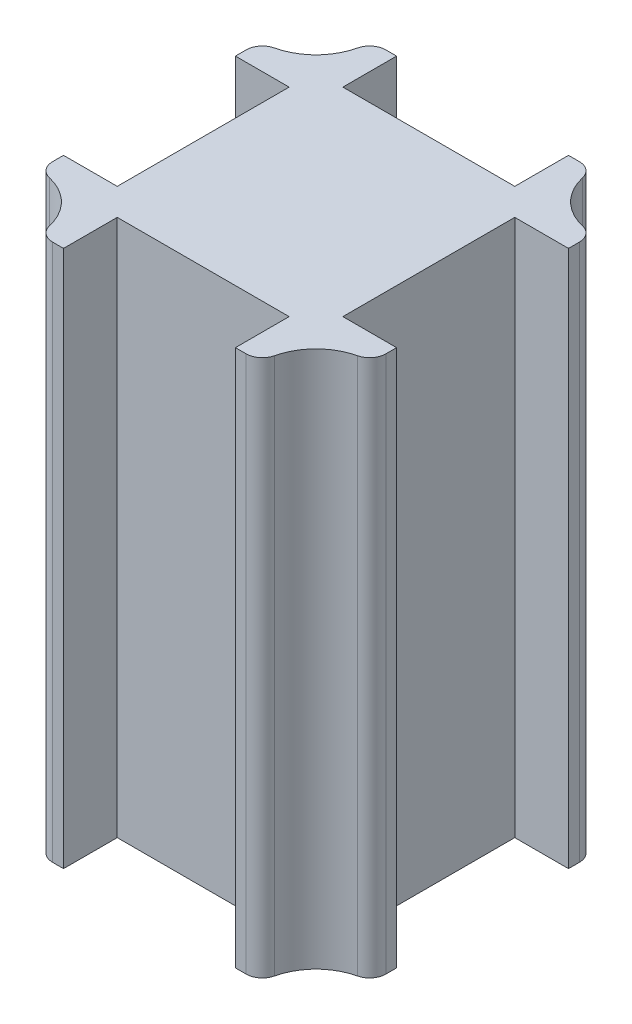
SolidWorks part; units mm, degrees
ref_plane "Front Plane" through (0, 0, 0) normal (0, 0, 1) x (1, 0, 0)
ref_plane "Top Plane" through (0, 0, 0) normal (0, 1, 0) x (1, 0, 0)
ref_plane "Right Plane" through (0, 0, 0) normal (1, 0, 0) x (0, 0, -1)
sketch "Sketch5" plane through (0, 3, 0) normal (0, 1, 0) x (1, 0, 0)
  line L0 (7.5, -348) -> (7.5, 348) construction
  line L1 (-15.5, 15.5) -> (15.5, 15.5)
  line L2 (-15.5, 15.5) -> (-15.5, -15.5)
  line L3 (-15.5, -15.5) -> (15.5, -15.5)
  line L4 (15.5, 15.5) -> (15.5, -15.5)
  line L5 (-15.5, 15.5) -> (15.5, -15.5) construction
  line L6 (-15.5, -15.5) -> (15.5, 15.5) construction
  line L7 (-348, 7.5) -> (348, 7.5) construction
  point P0 (0, 0)
  dimension "D1" = 8
  dimension "D2" = 8
extrude "Boss-Extrude2" add sketch "Sketch5" along normal blind 50
sketch "Sketch6" plane through (0, 53, 0) normal (0, 1, 0) x (1, 0, 0)
  line L1 (-15.5, 15.5) -> (-15.5, -15.5) construction
  line L5 (-15.5, -8) -> (-15.5, 8)
  line L15 (-15.5, 8) -> (-10.5, 8)
  line L16 (-10.5, 8) -> (-10.5, -8)
  line L17 (-10.5, -8) -> (-15.5, -8)
  line L18 (-348, 7.5) -> (348, 7.5) construction
  line L19 (348, -7.5) -> (-348, -7.5) construction
  line L20 (-7.5, 348) -> (-7.5, -348) construction
  dimension "D1" = 0.5
  dimension "D2" = 0.5
  dimension "D3" = 3
extrude "Cut-Extrude1" cut sketch "Sketch6" against normal blind 50
ref_point "Point1"
ref_axis "Axis1" through (0, 0, 0) along (0, 1, 0)
pattern_circular "CirPattern1" count 4 every 90 about axis through (0, 0, 0) along (0, 1, 0) of "Cut-Extrude1"
sketch "Sketch7" plane through (0, 53, 0) normal (0, 1, 0) x (1, 0, 0)
  circle A0 centre (-15.5, -15.5) radius 5.1641
extrude "Cut-Extrude2" cut sketch "Sketch7" against normal blind 50
pattern_circular "CirPattern2" count 4 every 90 about axis through (0, 0, 0) along (0, 1, 0) of "Cut-Extrude2"
fillet "Fillet1" radius 1.5 8 edges at (-15.5, 28, -10.3359) (-10.3359, 28, -15.5) (10.3359, 28, -15.5) (15.5, 28, -10.3359) (15.5, 28, 10.3359) (10.3359, 28, 15.5) (-10.3359, 28, 15.5) (-15.5, 28, 10.3359)
sketch "Sketch8" plane through (0, 3, 0) normal (0, -1, 0) x (1, 0, 0)
  circle A0 centre (0, 0) radius 4.25
  dimension "D1" = 8.5
extrude "Cut-Extrude3" cut sketch "Sketch8" against normal blind 1.5
